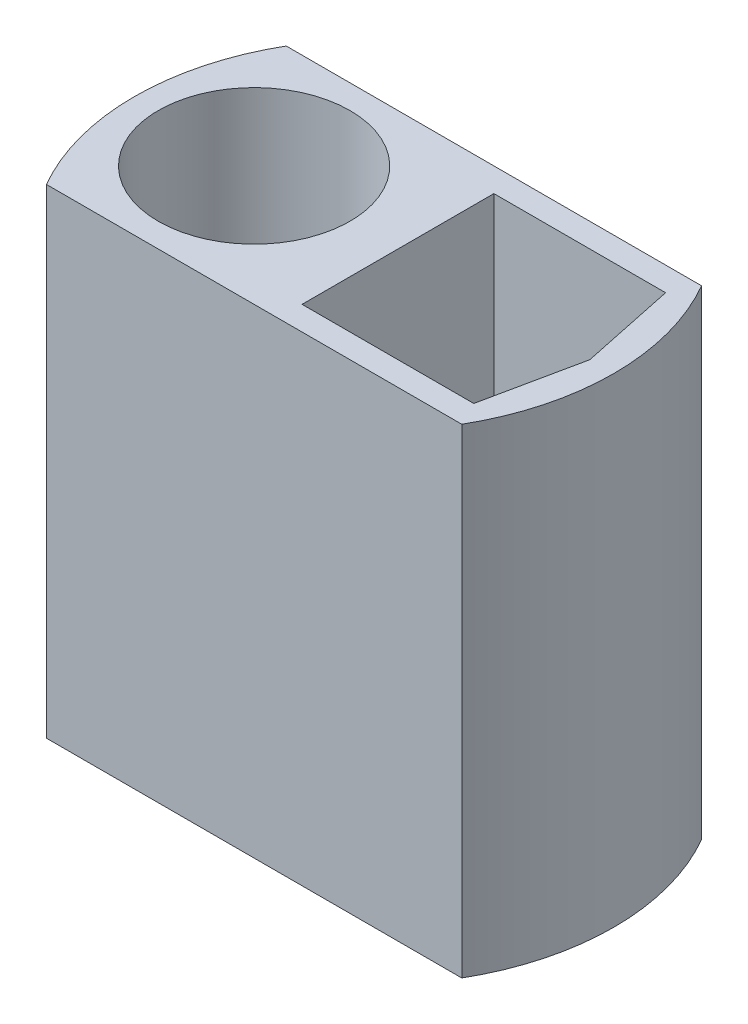
SolidWorks part; units mm, degrees
ref_plane "Front Plane" through (0, 0, 0) normal (0, 0, 1) x (1, 0, 0)
ref_plane "Top Plane" through (0, 0, 0) normal (0, 1, 0) x (1, 0, 0)
ref_plane "Right Plane" through (0, 0, 0) normal (1, 0, 0) x (0, 0, -1)
sketch "Sketch1" plane through (0, 0, 0) normal (0, 1, 0) x (1, 0, 0)
  line L0 (-7.7754, 6.35) -> (-10.9985, 6.35)
  line L1 (-7.7754, 6.35) -> (10.9985, 6.35)
  line L2 (-10.9985, -6.35) -> (10.9985, -6.35)
  line L3 (1.27, 0) -> (1.27, 5.08)
  line L4 (1.27, 5.08) -> (10.3639, 5.08)
  line L5 (10.3639, 5.08) -> (11.43, 0)
  line L6 (11.43, 0) -> (10.3639, -5.08)
  line L7 (10.3639, -5.08) -> (1.27, -5.08)
  line L8 (1.27, -5.08) -> (1.27, 0)
  circle A0 centre (0, 0) radius 12.7
  circle A1 centre (-6.35, 0) radius 5.08
  circle A4 centre (-7.62, 0) radius 0.635
  circle A5 centre (-5.08, 0) radius 0.635
  circle A7 centre (3.5281, 2.54) radius 0.635
  circle A8 centre (6.35, 2.54) radius 0.635
  circle A9 centre (9.2022, 2.54) radius 0.635
  dimension "D1" = 25.4
  dimension "D2" = 10.16
  dimension "D8" = 1.27
  dimension "D9" = 1.27
  dimension "D14" = 1.27
  dimension "D15" = 1.27
  dimension "D16" = 1.27
  dimension "D4" = 1.27
  dimension "D5" = 1.27
  dimension "D6" = 6.35
  dimension "D7" = 6.35
extrude "Boss-Extrude4" add sketch "Sketch1" along normal blind 25.4 contours L2 A0 L1 L0 A1 region at (-0.6221, 0, 0)
extrude "Boss-Extrude5" add sketch "Sketch1<9>" along normal blind 1.27 contours A1 A5 A4 | A9 A8 A7 region at (6.0774, 0, 0.1027) region at (-6.35, 0, 0)
sketch "Sketch1<9>" plane through (0, 0, 0) normal (0, 1, 0) x (1, 0, 0) same geometry as "Sketch1"
